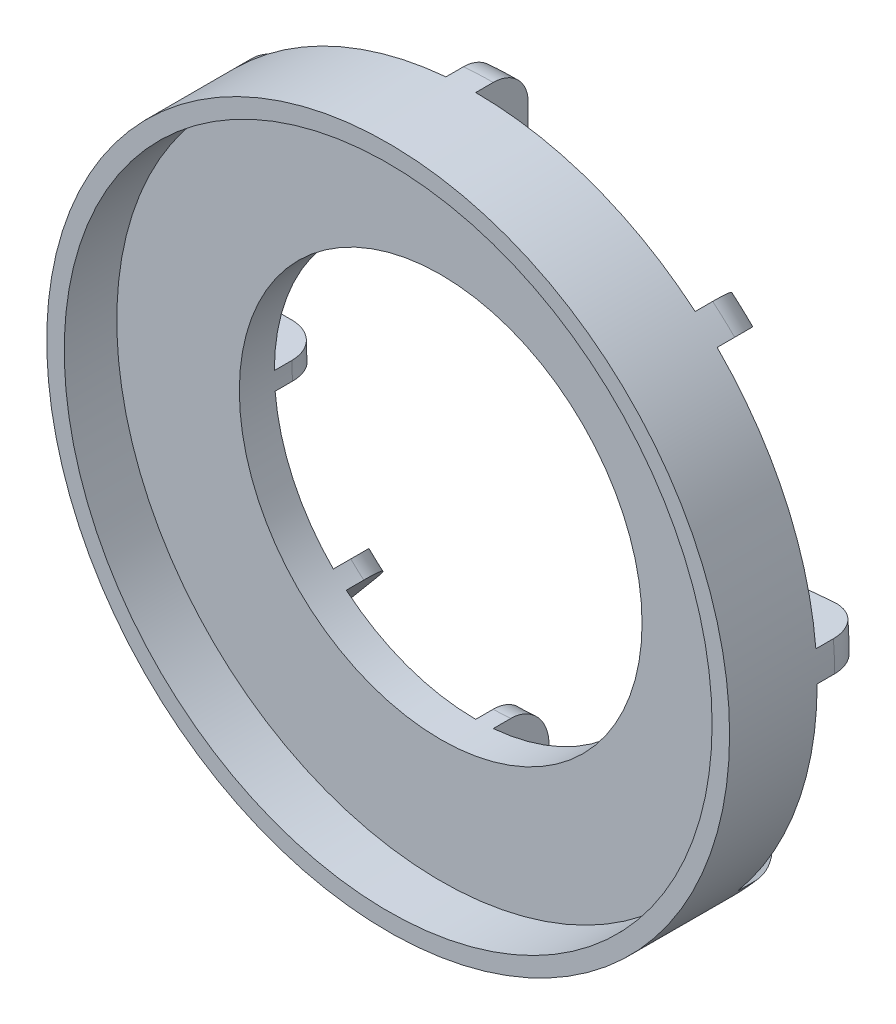
SolidWorks part; units mm, degrees
ref_plane "Front Plane" through (0, 0, 0) normal (0, 0, 1) x (1, 0, 0)
ref_plane "Top Plane" through (0, 0, 0) normal (0, 1, 0) x (1, 0, 0)
ref_plane "Right Plane" through (0, 0, 0) normal (1, 0, 0) x (0, 0, -1)
sketch "Sketch1" plane through (0, 0, 0) normal (0, 0, 1) x (1, 0, 0)
  circle A0 centre (0, 0) radius 18.5
  circle A1 centre (0, 0) radius 11.5
  circle A2 centre (0, 0) radius 19.5
  dimension "D1" = 37
  dimension "D2" = 23
  dimension "D3" = 1
extrude "Boss-Extrude1" add sketch "Sketch1" along normal blind 2 contours A0 A1 region at (-17.9767, 0, 0)
extrude "Boss-Extrude2" add sketch "Sketch1<4>" along normal blind 5 contours A2 A0 region at (-18.9485, 0, 0)
sketch "Sketch1<4>" plane through (0, 0, 0) normal (0, 0, 1) x (1, 0, 0) same geometry as "Sketch1"
sketch "Sketch2" plane through (0, 0, 0) normal (0, 0, -1) x (-1, 0, 0)
  line L0 (0, 19.5) -> (0, 11.5)
  line L1 (1.0023, 11.4562) -> (1.6995, 19.4258)
  line L2 (0, 0) -> (1.6995, 19.4258) construction
  line L3 (0, 0) -> (0, 19.5) construction
  circle A1 centre (0, 0) radius 19.5 construction
  arc A2 (0, 11.5) -> (1.0023, 11.4562) centre (0, 0) cw
  circle A3 centre (0, 0) radius 11.5 construction
  arc A4 (1.6995, 19.4258) -> (0, 19.5) centre (0, 0) ccw
  circle M7 centre (0, 0) radius 11.5
  circle M8 centre (0, 0) radius 19.5
  dimension "D1" = 5
extrude "Boss-Extrude3" add sketch "Sketch2" along normal blind 3 contours L1 L0 M7 M8 region at (-0.6909, 15.824, 0)
fillet "Fillet2" radius 2 2 edges at (-0.8506, 19.4814, -3) (-0.5016, 11.4891, -3)
ref_axis "Axis1" through (0, 0, 5.4) along (0, 0, -1)
pattern_circular "CirPattern1" count 8 every 45 about axis through (0, 0, 5.4) along (0, 0, -1) of "Boss-Extrude3", "Fillet2"
